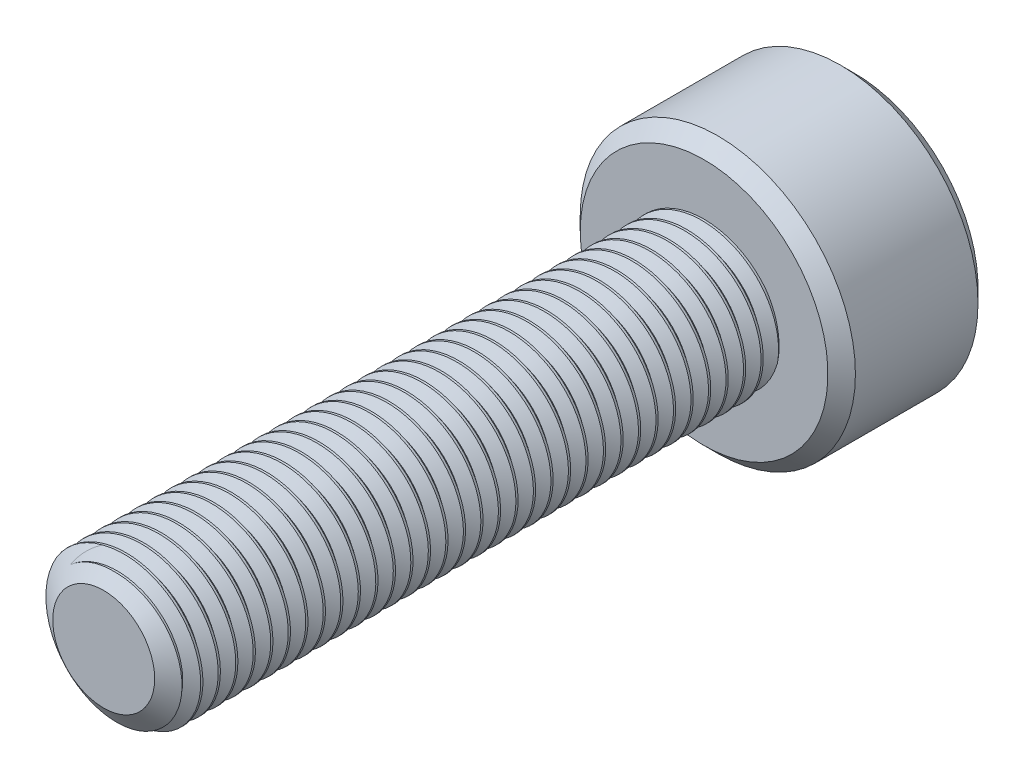
SolidWorks part; units mm, degrees
other "DetailItem1"
ref_plane "Front Plane" through (0, 0, 0) normal (0, 0, 1) x (1, 0, 0)
ref_plane "Top Plane" through (0, 0, 0) normal (0, 1, 0) x (1, 0, 0)
ref_plane "Right Plane" through (0, 0, 0) normal (1, 0, 0) x (0, 0, -1)
sketch "Sketch1" plane through (0, 0, 0) normal (0, 0, 1) x (1, 0, 0)
  circle A0 centre (0, 0) radius 1.5
  dimension "OD" = 3
extrude "Extrude1" add sketch "Sketch1" against normal blind 12
sketch "Sketch2" plane through (0, 0, 0) normal (0, 0, 1) x (1, 0, 0)
  circle A0 centre (0, 0) radius 1.5 construction
  circle A1 centre (0, 0) radius 1.5
curve "Helix/Spiral1" pitch 0.35 height 12.35 turns 35.2857 parameters "pitch"=0.35
sketch "Sketch3" plane through (0, 0, 0) normal (1, 0, 0) x (0, 0, -1)
  line L0 (-0.3062, 1.5) -> (-0.175, 1.2727)
  line L1 (-0.175, 1.2727) -> (-0.1313, 1.2727)
  line L2 (-0.1313, 1.2727) -> (0, 1.5)
  line L3 (-0.3062, 1.5) -> (0, 1.5)
  line L4 (-0.1531, 1.5) -> (-0.1531, 1.2727) construction
  line L5 (-0.2406, 1.3863) -> (-0.0656, 1.3863) construction
  line L6 (0, 1.5) -> (0, -1.5) construction
  dimension "D1" = 0.0437
  dimension "D2" = 0.175
  dimension "D3" = 60
sweep "Cut-Sweep1" cut profiles "Sketch3" path "Helix/Spiral1"
sketch "Sketch4" plane through (0, 0, 0) normal (1, 0, 0) x (0, 0, -1)
  line L0 (0.337, 1.5) -> (0, 1.0187)
  line L1 (0, 1.0187) -> (0, 1.5)
  line L2 (0.337, 1.5) -> (0, 1.5)
  line L3 (-0.3062, 1.5) -> (0, 1.5) construction
  line L4 (0, 0) -> (7.0209, 0) construction
  dimension "D1" = 55
  dimension "D2" = 0.254
revolve "Cut-Revolve1" cut sketch "Sketch4" angle 360 about L4
sketch "Sketch6" plane through (0, 0, -12) normal (0, 0, -1) x (-1, 0, 0)
  circle A0 centre (0, 0) radius 2.75
  dimension "head dia" = 5.5
extrude "Extrude2" add sketch "Sketch6" along normal blind 3
sketch "Sketch7" plane through (0, 0, -15) normal (0, 0, -1) x (-1, 0, 0)
  line L1 (0, 1.4434) -> (-1.25, 0.7217)
  line L2 (-1.25, 0.7217) -> (-1.25, -0.7217)
  line L3 (-1.25, -0.7217) -> (0, -1.4434)
  line L4 (0, -1.4434) -> (1.25, -0.7217)
  line L5 (1.25, -0.7217) -> (1.25, 0.7217)
  line L6 (1.25, 0.7217) -> (0, 1.4434)
  circle A0 centre (0, 0) radius 1.25 construction
  dimension "hex dia" = 2.5
extrude "Cut-Extrude1" cut sketch "Sketch7" against normal blind 1.875
sketch "Sketch8" plane through (0, 0, -15) normal (0, 0, -1) x (-1, 0, 0)
  circle A0 centre (0, 0) radius 1.4434
extrude "Cut-Extrude2" cut sketch "Sketch8" against normal through all draft 45
chamfer "Chamfer1" distance 0.275 angle 45 2 edges at (-2.75, 0, -15) (-2.75, 0, -12)
sketch "Sketch10" plane through (0, 0, -12) normal (0, 0, 1) x (1, 0, 0)
  circle A1 centre (0, 0) radius 1.5
  circle A2 centre (0, 0) radius 1.5
  dimension "D1" = 0
ref_plane "Plane1" through (0, 0, -7) normal (0, 0, 1) x (1, 0, 0)
extrude "partial thread" [suppressed] add sketch "Sketch10" along normal up to surface (3 mm away) separate body
chamfer "Chamfer2" [suppressed] distance 0.06 angle 45
combine bodies "Combine1" [suppressed] operation type add bodies to combine 107 108
sketch "Sketch9" plane through (0, 0, 0) normal (1, 0, 0) x (0, 0, -1)
  line L0 (0, 1.5) -> (0, -1.5) construction
  line L1 (0.875, 1.5) -> (0.875, -1.5) construction
  dimension "D1" = 0.875
equation "\"D3@Helix/Spiral1\" = \"screw length@Extrude1\"+\"pitch@Helix/Spiral1\""
equation "\"D1@Sketch3\" = \"pitch@Helix/Spiral1\"*.125"
equation "\"D2@Sketch3\" = \"pitch@Helix/Spiral1\"*.5"
equation "\"D1@Cut-Extrude1\" = \"hex dia@Sketch7\"*.75"
equation "\"D1@Chamfer1\" = \"head dia@Sketch6\"*.05"
equation "\"D1@Sketch9\" = \"pitch@Helix/Spiral1\"*2.5"
equation "\"D1@Chamfer2\"=\"OD@Sketch1\"*.02"
